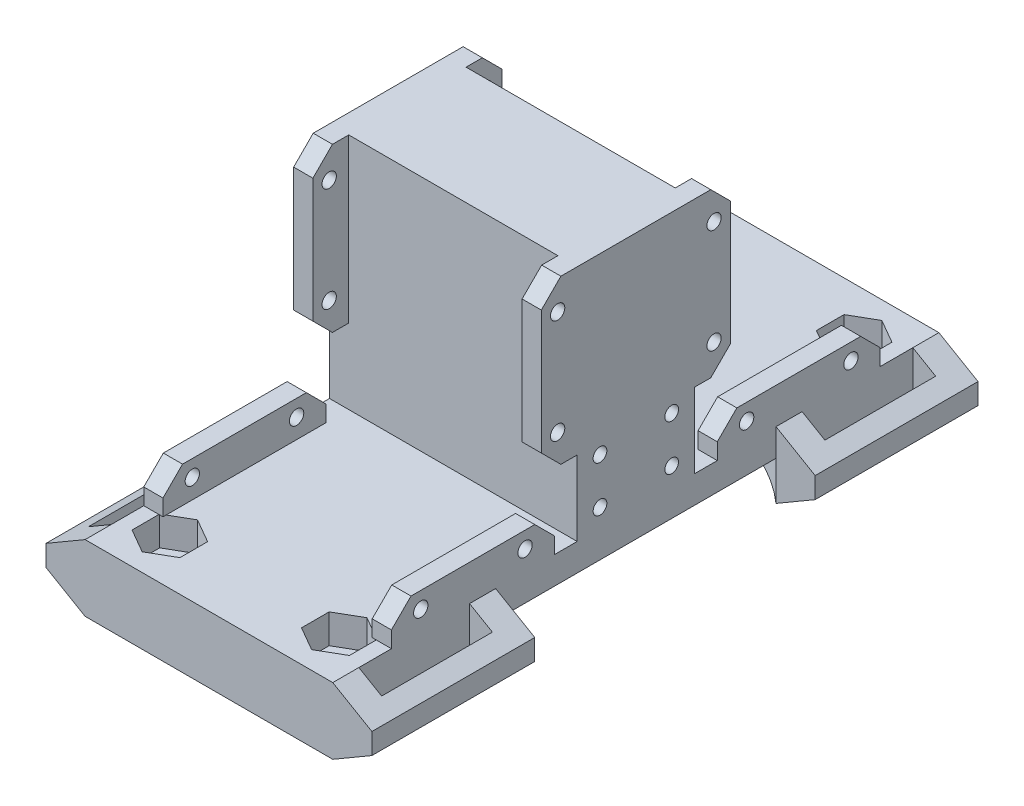
SolidWorks part; units mm, degrees
note: The reader was unsure of these and kept them because the rebuilt part matched: shared geometry of "Sketch3<2>", "Sketch9<2>".
ref_plane "Front Plane" through (0, 0, 0) normal (0, 0, 1) x (1, 0, 0)
ref_plane "Top Plane" through (0, 0, 0) normal (0, 1, 0) x (1, 0, 0)
ref_plane "Right Plane" through (0, 0, 0) normal (1, 0, 0) x (0, 0, -1)
sketch "Sketch1" plane through (0, 0, 0) normal (0, 0, 1) x (1, 0, 0)
  line L1 (19, -5.1) -> (-19, -5.1)
  line L2 (19, -5.1) -> (19, 5.1)
  line L3 (19, 5.1) -> (-19, 5.1)
  line L4 (-19, -5.1) -> (-19, 5.1)
  line L5 (19, -5.1) -> (-19, 5.1) construction
  line L6 (19, 5.1) -> (-19, -5.1) construction
  point P0 (0, 0)
  dimension "D1" = 10.2
  dimension "D2" = 38
extrude "Main_base" add sketch "Sketch1" along normal mid plane 93
sketch "Sketch2" plane through (0, -5.1, 0) normal (0, -1, 0) x (1, 0, 0)
  circle A0 centre (0, 0) radius 28.7
  dimension "D1" = 57.4
extrude "Free space" cut sketch "Sketch2" against normal blind 6
sketch "Sketch3" plane through (0, 0, 0) normal (0, 0, 1) x (1, 0, 0)
  line L1 (25, 1.6) -> (25, -1.6)
  line L2 (25, -1.6) -> (19, -5.1)
  line L3 (19, -5.1) -> (19, 5.1)
  line L4 (19, 0) -> (25, 0) construction
  line L5 (25, 1.6) -> (19, 5.1)
  line L6 (0, 0) -> (0, 5.1) construction
  line L7 (19, 5.1) -> (-19, 5.1) construction
  line L8 (-19, 0) -> (-25, 0) construction
  line L9 (-25, 1.6) -> (-19, 5.1)
  line L10 (-19, -5.1) -> (-19, 5.1)
  line L11 (-25, -1.6) -> (-19, -5.1)
  line L12 (-25, 1.6) -> (-25, -1.6)
  dimension "D1" = 6
  dimension "D2" = 3.5
extrude "Brackets1" add sketch "Sketch3" against normal up to vertex from surface
extrude "Brackets2" add sketch "Sketch3<2>" along normal up to vertex from surface
sketch "Sketch3<2>" plane through (0, 0, 0) normal (0, 0, 1) x (1, 0, 0) same geometry as "Sketch3"
sketch "Sketch5" plane through (0, 0, 0) normal (0, 1, 0) x (1, 0, 0)
  line L0 (19, -46.5) -> (19, -21.5102) construction
  line L1 (19, -25.5102) -> (22.5, -25.5102)
  line L2 (19, -25.5102) -> (19, -42.5)
  line L3 (19, -42.5) -> (22.5, -42.5)
  line L4 (22.5, -25.5102) -> (22.5, -42.5)
  line L5 (19, -21.5102) -> (25, -21.5102) construction
  line L6 (19, -46.5) -> (25, -46.5) construction
  line L7 (0, 0) -> (0, -46.5) construction
  line L8 (19, -46.5) -> (-19, -46.5) construction
  line L9 (-22.5, -25.5102) -> (-22.5, -42.5)
  line L10 (-19, -42.5) -> (-22.5, -42.5)
  line L11 (-19, -25.5102) -> (-19, -42.5)
  line L12 (-19, -25.5102) -> (-22.5, -25.5102)
  line L13 (0, 0) -> (19, 0) construction
  line L14 (19, -21.5102) -> (19, 21.5102) construction
  line L15 (-19, 25.5102) -> (-22.5, 25.5102)
  line L16 (-19, 25.5102) -> (-19, 42.5)
  line L17 (-19, 42.5) -> (-22.5, 42.5)
  line L18 (-22.5, 25.5102) -> (-22.5, 42.5)
  line L19 (22.5, 25.5102) -> (22.5, 42.5)
  line L20 (19, 42.5) -> (22.5, 42.5)
  line L21 (19, 25.5102) -> (19, 42.5)
  line L22 (19, 25.5102) -> (22.5, 25.5102)
  dimension "D1" = 4
  dimension "D2" = 4
  dimension "D3" = 3.5
extrude "Bracket holes" cut sketch "Sketch5" against normal through all both and the other way through all
sketch "Sketch6" plane through (0, 0, 0) normal (0, 1, 0) x (1, 0, 0)
  line L0 (0, 0) -> (0, 46.5) construction
  line L1 (19, 46.5) -> (-19, 46.5) construction
  line L2 (0, 0) -> (-19, 0) construction
  line L3 (-19, -21.5102) -> (-19, 21.5102) construction
  circle A0 centre (-13, 39.5) radius 2.25
  circle A1 centre (-13, -39.5) radius 2.25
  circle A2 centre (13, -39.5) radius 2.25
  circle A3 centre (13, 39.5) radius 2.25
  dimension "D1" = 4.5
  dimension "D2" = 39.5
  dimension "D3" = 13
extrude "Bolt holes" cut sketch "Sketch6" against normal through all both and the other way through all
sketch "Sketch7" plane through (0, 0, 0) normal (0, 1, 0) x (1, 0, 0)
  line L0 (13, 39.5) -> (0, 39.5) construction
  line L1 (13, 35.2565) -> (16.675, 37.3782)
  line L2 (16.675, 37.3782) -> (16.675, 41.6218)
  line L3 (16.675, 41.6218) -> (13, 43.7435)
  line L4 (13, 43.7435) -> (9.325, 41.6218)
  line L5 (9.325, 41.6218) -> (9.325, 37.3782)
  line L6 (9.325, 37.3782) -> (13, 35.2565)
  line L7 (0, 39.5) -> (0, -39.5) construction
  line L8 (0, 0) -> (19, 0) construction
  line L9 (19, -21.5102) -> (19, 21.5102) construction
  line L10 (13, 43.7435) -> (13, 35.2565) construction
  line L11 (-13, 43.7435) -> (-13, 35.2565) construction
  line L12 (-9.325, 37.3782) -> (-13, 35.2565)
  line L13 (-9.325, 41.6218) -> (-9.325, 37.3782)
  line L14 (-13, 43.7435) -> (-9.325, 41.6218)
  line L15 (-16.675, 41.6218) -> (-13, 43.7435)
  line L16 (-16.675, 37.3782) -> (-16.675, 41.6218)
  line L17 (-13, 35.2565) -> (-16.675, 37.3782)
  line L18 (-13, -43.7435) -> (-13, -35.2565) construction
  line L19 (13, -43.7435) -> (13, -35.2565) construction
  line L20 (13, -39.5) -> (0, -39.5) construction
  line L21 (-13, -35.2565) -> (-16.675, -37.3782)
  line L22 (-16.675, -37.3782) -> (-16.675, -41.6218)
  line L23 (-16.675, -41.6218) -> (-13, -43.7435)
  line L24 (-13, -43.7435) -> (-9.325, -41.6218)
  line L25 (-9.325, -41.6218) -> (-9.325, -37.3782)
  line L26 (-9.325, -37.3782) -> (-13, -35.2565)
  line L27 (9.325, -37.3782) -> (13, -35.2565)
  line L28 (9.325, -41.6218) -> (9.325, -37.3782)
  line L29 (13, -43.7435) -> (9.325, -41.6218)
  line L30 (16.675, -41.6218) -> (13, -43.7435)
  line L31 (16.675, -37.3782) -> (16.675, -41.6218)
  line L32 (13, -35.2565) -> (16.675, -37.3782)
  circle A0 centre (13, 39.5) radius 3.675 construction
  circle A1 centre (-13, 39.5) radius 3.675 construction
  circle A2 centre (-13, -39.5) radius 3.675 construction
  circle A3 centre (13, -39.5) radius 3.675 construction
  dimension "D1" = 8.487
extrude "Nut slots" cut sketch "Sketch7" against normal blind 4.5 from surface at 5.1 starting at face at (13, 5.1, -41.75)
sketch "Sketch8" plane through (0, 5.1, 0) normal (0, 1, 0) x (1, 0, 0)
  line L0 (-19, -21.5102) -> (-19, 21.5102) construction
  line L1 (-19, 9) -> (19, 9)
  line L2 (-19, 9) -> (-19, -9)
  line L3 (-19, -9) -> (19, -9)
  line L4 (19, 9) -> (19, -9)
  line L5 (19, -21.5102) -> (19, 21.5102) construction
  line L6 (-19, 0) -> (19, 0) construction
  dimension "D1" = 18
extrude "Motor base" add sketch "Sketch8" along normal blind 36.5
sketch "Sketch9" plane through (0, 0, 0) normal (1, 0, 0) x (0, 0, -1)
  line L0 (-9, 41.6) -> (-9, 5.1) construction
  line L1 (-9, 41.6) -> (-11.5, 41.6)
  line L2 (-9, 41.6) -> (-9, 16.6)
  line L3 (-9, 16.6) -> (-11.5, 16.6)
  line L4 (-14.5, 38.6) -> (-14.5, 19.6)
  line L5 (-25.5102, 5.1) -> (-42.5, 5.1) construction
  line L6 (-37.5, 5.1) -> (-12.5, 5.1)
  line L7 (-37.5, 5.1) -> (-37.5, 7.6)
  line L8 (-34.5, 10.6) -> (-15.5, 10.6)
  line L9 (-12.5, 5.1) -> (-12.5, 7.6)
  line L10 (-37.5, 7.6) -> (-34.5, 10.6)
  line L11 (-15.5, 10.6) -> (-12.5, 7.6)
  line L12 (-11.5, 16.6) -> (-14.5, 19.6)
  line L13 (-11.5, 41.6) -> (-14.5, 38.6)
  line L14 (0, 0) -> (0, 41.6) construction
  line L15 (-9, 41.6) -> (9, 41.6) construction
  line L16 (11.5, 41.6) -> (14.5, 38.6)
  line L17 (11.5, 16.6) -> (14.5, 19.6)
  line L18 (15.5, 10.6) -> (12.5, 7.6)
  line L19 (37.5, 7.6) -> (34.5, 10.6)
  line L20 (12.5, 5.1) -> (12.5, 7.6)
  line L21 (34.5, 10.6) -> (15.5, 10.6)
  line L22 (37.5, 5.1) -> (37.5, 7.6)
  line L23 (37.5, 5.1) -> (12.5, 5.1)
  line L24 (14.5, 38.6) -> (14.5, 19.6)
  line L25 (9, 16.6) -> (11.5, 16.6)
  line L26 (9, 41.6) -> (9, 16.6)
  line L27 (9, 41.6) -> (11.5, 41.6)
  circle A0 centre (-33, 8.1) radius 1.1
  circle A1 centre (-17, 8.1) radius 1.1
  circle A2 centre (-12, 21.1) radius 1.1
  circle A3 centre (-12, 37.1) radius 1.1
  circle A4 centre (12, 37.1) radius 1.1
  circle A5 centre (12, 21.1) radius 1.1
  circle A6 centre (17, 8.1) radius 1.1
  circle A7 centre (33, 8.1) radius 1.1
  point P1 (-14.5, 16.6)
  point P3 (-14.5, 41.6)
  point P7 (-12.5, 10.6)
  point P8 (-37.5, 10.6)
  point P54 (37.5, 10.6)
  point P55 (12.5, 10.6)
  point P56 (14.5, 41.6)
  point P57 (14.5, 16.6)
  dimension "D6" = 2.2
  dimension "D1" = 25
  dimension "D2" = 25
  dimension "D3" = 3.5
  dimension "D4" = 5.5
  dimension "D5" = 5.5
  dimension "D7" = 4.5
  dimension "D12" = 3
  dimension "D13" = 16
  dimension "D14" = 4.5
  dimension "D15" = 3
  dimension "D16" = 16
extrude "Motor brackets1" add sketch "Sketch9" against normal blind 2.95 from surface at 19 starting at face at (19, 13.175, 0)
extrude "Motor brackets2" add sketch "Sketch9<2>" along normal blind 2.95 from surface at -19 starting at face at (-19, 13.175, 0)
sketch "Sketch9<2>" plane through (0, 0, 0) normal (1, 0, 0) x (0, 0, -1) same geometry as "Sketch9"
sketch "Sketch10" plane through (-19, 0, 0) normal (-1, 0, 0) x (0, 0, 1)
  line L0 (21.5102, 0.9) -> (-21.5102, 0.9) construction
  line L1 (-5.5, 6.8) -> (-5.5, 14.9) construction
  line L2 (-21.5102, 0.9) -> (21.5102, 0.9) construction
  line L3 (-9, 10.85) -> (-2, 10.85) construction
  line L4 (-9, 16.6) -> (-9, 5.1) construction
  line L6 (0, 0.9) -> (0, 24.5668) construction
  line L7 (5.5, 6.8) -> (5.5, 14.9) construction
  circle A0 centre (-5.5, 14.9) radius 1.05
  circle A1 centre (-5.5, 7.9) radius 1.05
  circle A2 centre (5.5, 7.9) radius 1.05
  circle A3 centre (5.5, 14.9) radius 1.05
  point P16 (-5.5, 10.85)
  point P25 (0, 0)
  dimension "D1" = 2.1
  dimension "D2" = 14
  dimension "D3" = 7
  dimension "D4" = 5.5
extrude "motor_driver_mount_holes1" cut sketch "Sketch10" against normal blind 10
mirror "motor_driver_mount_holes2" about plane through (0, 0, 0) normal (1, 0, 0) of "motor_driver_mount_holes1"
